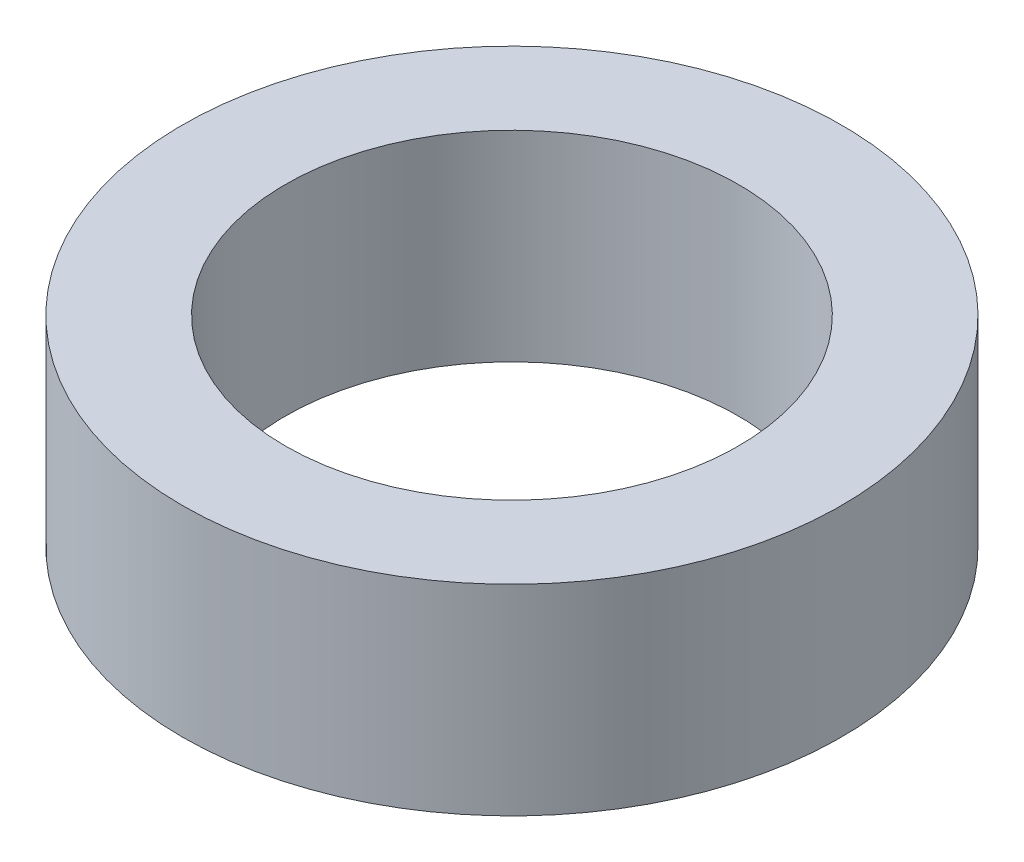
SolidWorks part; units mm, degrees
ref_plane "Front" through (0, 0, 0) normal (0, 0, 1) x (1, 0, 0)
ref_plane "Top" through (0, 0, 0) normal (0, 1, 0) x (1, 0, 0)
ref_plane "Right" through (0, 0, 0) normal (1, 0, 0) x (0, 0, -1)
sketch "Sketch1" plane through (0, 0, 0) normal (0, 1, 0) x (1, 0, 0)
  circle A0 centre (0, 0) radius 6.325
  circle A1 centre (0, 0) radius 9.2
extrude "Boss-Extrude1" add sketch "Sketch1" along normal blind 5.6
